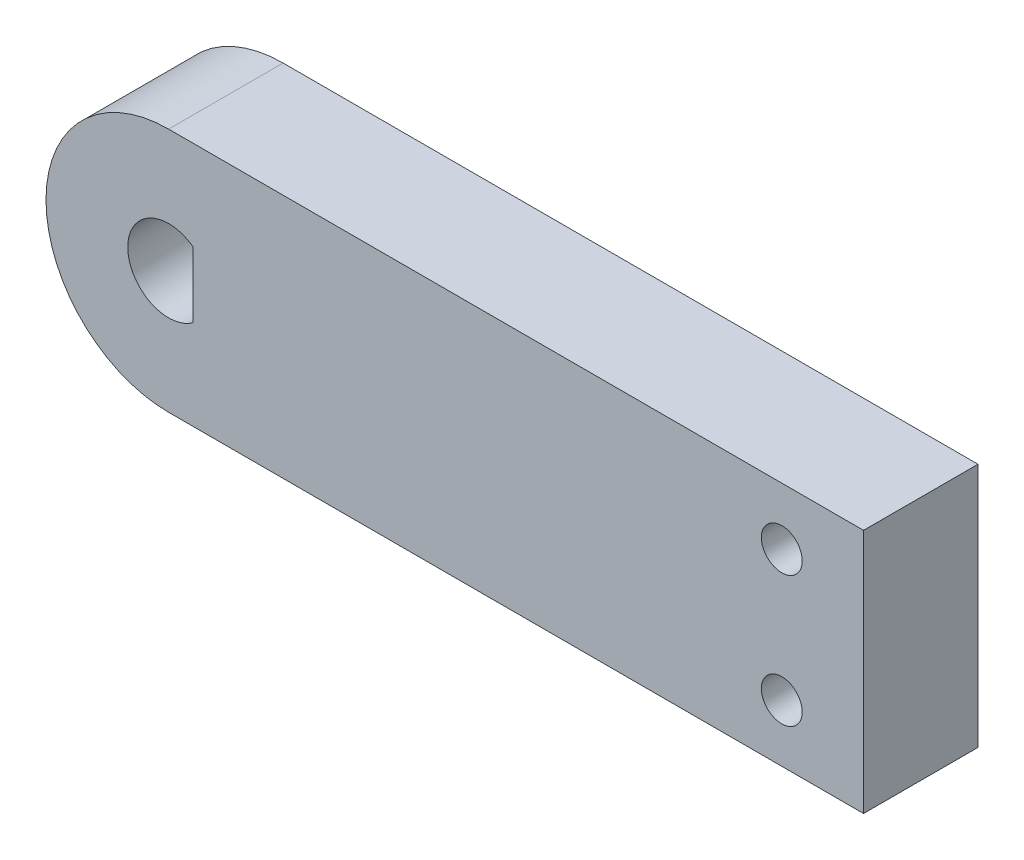
SolidWorks part; units mm, degrees
ref_plane "Front Plane" through (0, 0, 0) normal (0, 0, 1) x (1, 0, 0)
ref_plane "Top Plane" through (0, 0, 0) normal (0, 1, 0) x (1, 0, 0)
ref_plane "Right Plane" through (0, 0, 0) normal (1, 0, 0) x (0, 0, -1)
sketch "Sketch1" plane through (0, 0, 0) normal (0, 0, 1) x (1, 0, 0)
  line L1 (-31.75, -9.525) -> (31.75, -9.525)
  line L2 (-31.75, -9.525) -> (-31.75, 9.525)
  line L3 (-31.75, 9.525) -> (31.75, 9.525)
  line L4 (31.75, -9.525) -> (31.75, 9.525)
  line L5 (-31.75, -9.525) -> (31.75, 9.525) construction
  line L6 (-31.75, 9.525) -> (31.75, -9.525) construction
  point P0 (0, 0)
  dimension "D1" = 19.05
  dimension "D2" = 63.5
extrude "Boss-Extrude1" add sketch "Sketch1" along normal mid plane 8.89
sketch "Sketch2" plane through (0, 0, 4.445) normal (0, 0, 1) x (1, 0, 0)
  line L0 (0, 0) -> (25.4, 0) construction
  line L1 (25.4, 0) -> (25.4, 5.08) construction
  line L2 (25.4, 0) -> (25.4, -5.08) construction
  circle A0 centre (25.4, 5.08) radius 1.5875
  circle A1 centre (25.4, -5.08) radius 1.5875
  dimension "D2" = 3.175
  dimension "D1" = 25.4
  dimension "D3" = 5.08
extrude "Cut-Extrude1" cut sketch "Sketch2" against normal blind 12.7
fillet "Fillet1" radius 9.525 2 edges at (-31.75, -9.525, 0) (-31.75, 9.525, 0)
sketch "Sketch3" plane through (0, 0, 4.445) normal (0, 0, 1) x (1, 0, 0)
  line L0 (-20.32, 2.54) -> (-20.32, -2.54)
  arc A0 (-20.32, 2.54) -> (-20.32, -2.54) centre (-22.225, 0) ccw
  dimension "D1" = 6.35
  dimension "D2" = 5.08
extrude "Cut-Extrude2" cut sketch "Sketch3" against normal through all both and the other way through all
